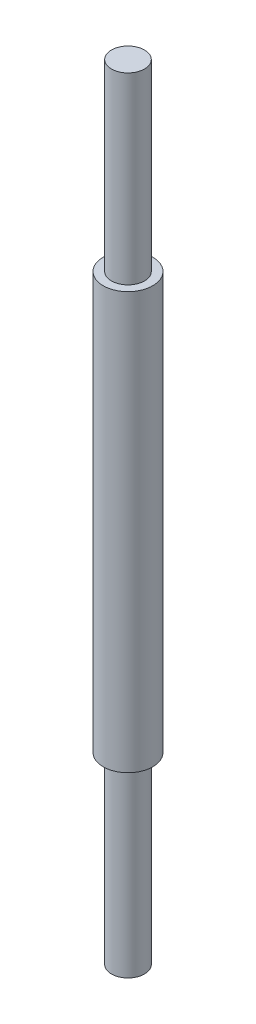
SolidWorks part; units mm, degrees
ref_plane "Front Plane" through (0, 0, 0) normal (0, 0, 1) x (1, 0, 0)
ref_plane "Top Plane" through (0, 0, 0) normal (0, 1, 0) x (1, 0, 0)
ref_plane "Right Plane" through (0, 0, 0) normal (1, 0, 0) x (0, 0, -1)
sketch "Sketch1" plane through (0, 0, 0) normal (0, 1, 0) x (1, 0, 0)
  circle A0 centre (0, 0) radius 4
  circle A1 centre (0, 0) radius 6
  dimension "D1" = 8
  dimension "D2" = 12
extrude "Boss-Extrude1" add sketch "Sketch1" along normal mid plane 190 contours A0 region at (0, 0, 0)
extrude "Boss-Extrude2" add sketch "Sketch1<3>" along normal mid plane 101
sketch "Sketch1<3>" plane through (0, 0, 0) normal (0, 1, 0) x (1, 0, 0) same geometry as "Sketch1"
